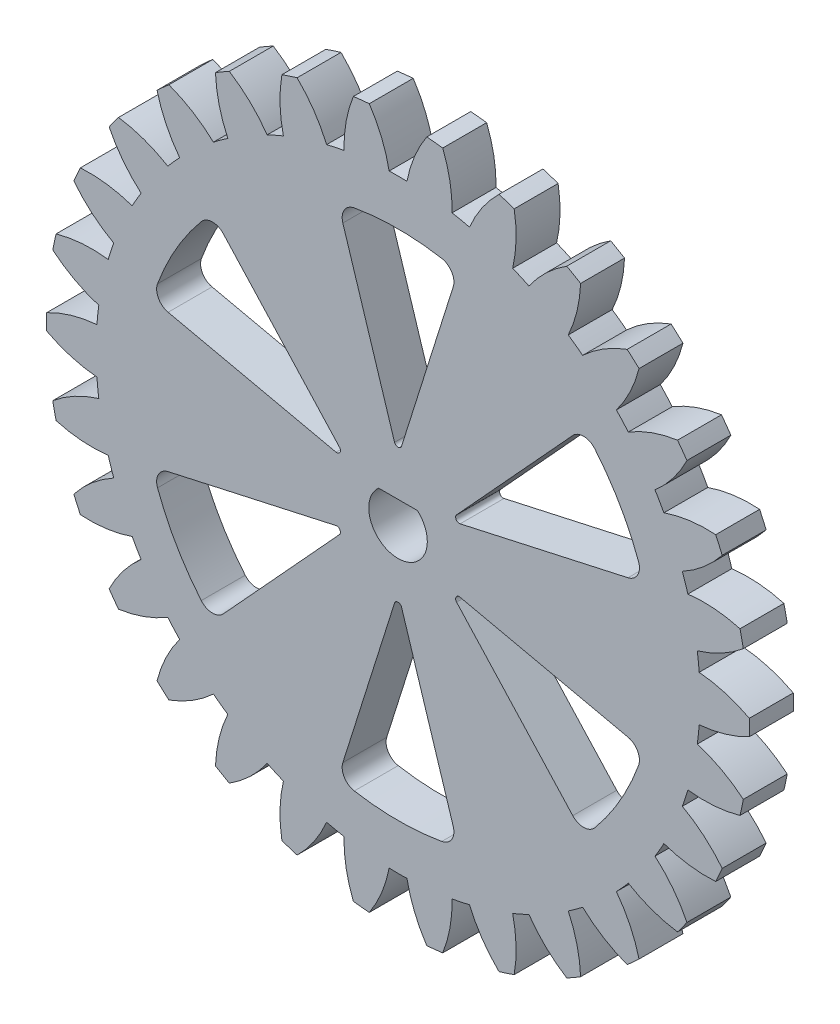
SolidWorks part; units mm, degrees
ref_plane "Front Plane" through (0, 0, 0) normal (0, 0, 1) x (1, 0, 0)
ref_plane "Top Plane" through (0, 0, 0) normal (0, 1, 0) x (1, 0, 0)
ref_plane "Right Plane" through (0, 0, 0) normal (1, 0, 0) x (0, 0, -1)
sketch "Sketch1" plane through (0, 0, 0) normal (0, 0, 1) x (1, 0, 0)
  circle A0 centre (0, 0) radius 24
  dimension "addendumDiameter" = 48
extrude "Boss-Extrude1" add sketch "Sketch1" along normal blind 3
sketch "Sketch2" plane through (0, 0, 3) normal (0, 0, 1) x (1, 0, 0)
  circle A0 centre (0, 0) radius 22.5 construction
  circle A1 centre (0, 0) radius 21.1431 construction
  circle A2 centre (0, 0) radius 20.625 construction
  dimension "D1" = 41.25
  dimension "D2" = 42.2862
  dimension "D3" = 45
sketch "Sketch3" plane through (0, 0, 3) normal (0, 0, 1) x (1, 0, 0)
  line L0 (0, 0) -> (0, 38.0024) construction
  line L1 (0, 0) -> (-1.8856, 17.9401) construction
  line L2 (-1.177, 22.4692) -> (-2.3487, 22.346) construction
  arc A0 (-1.965, 23.9194) -> (-0.6079, 20.616) centre (-9.4458, 18.9158) cw
  circle A1 centre (0, 0) radius 21.1431 construction
  circle A2 centre (0, 0) radius 24 construction
  circle A3 centre (0, 0) radius 20.625 construction
  arc A4 (1.965, 23.9194) -> (0.6079, 20.616) centre (9.4458, 18.9158) ccw
  arc A5 (-1.965, 23.9194) -> (1.965, 23.9194) centre (0, 0) cw
  arc A6 (0.6079, 20.616) -> (-0.6079, 20.616) centre (0, 0) ccw
  circle A7 centre (0, 0) radius 22.5 construction
  dimension "D2" = 9
  dimension "D1" = 6
  dimension "D3" = 1.1781
extrude "Cut-Extrude1" cut sketch "Sketch3" against normal through all
ref_axis "Axis2" through (0, 0, 3) along (0, 0, -1)
pattern_circular "CirPattern1" count 30 over 360 about axis through (0, 0, 3) along (0, 0, -1) of "Cut-Extrude1"
sketch "Sketch7" [suppressed] plane through (0, 0, 6.36) normal (0, 0, 1) x (1, 0, 0)
  circle A0 centre (0, 0) radius 2.6
  dimension "D1" = 5.2
sketch "Sketch9" plane through (0, 0, 3) normal (0, 0, 1) x (1, 0, 0)
  line L0 (-1.3229, 1.5) -> (1.3229, 1.5)
  arc A0 (-1.3229, 1.5) -> (1.3229, 1.5) centre (0, 0) ccw
  point P5 (0, 1.5)
  dimension "D1" = 4
  dimension "D2" = 1.5
extrude "Cut-Extrude7" cut sketch "Sketch9" against normal blind 10
sketch "Sketch10" plane through (0, 0, 3) normal (0, 0, 1) x (1, 0, 0)
  line L0 (0, 4) -> (-4.1028, 17.0123)
  line L2 (4.1028, 17.0123) -> (0, 4)
  arc A0 (-4.1028, 17.0123) -> (4.1028, 17.0123) centre (0, 0) cw
  arc A1 (-1.3229, 1.5) -> (1.3229, 1.5) centre (0, 0) ccw construction
  dimension "D1" = 17.5
  dimension "D3" = 4
  dimension "D4" = 35
ref_axis "Axis3" through (0, 0, 3) along (0, 0, 1)
extrude "Cut-Extrude8" cut sketch "Sketch10" against normal through all both and the other way through all
fillet "Fillet1" radius 1 2 edges at (4.1028, 17.0123, 1.5) (-4.1028, 17.0123, 1.5)
fillet "Fillet2" radius 0.25 1 edges at (0, 4, 1.5)
pattern_circular "CirPattern2" count 6 over 360 about axis through (0, 0, 3) along (0, 0, 1) of "Fillet2", "Cut-Extrude8", "Fillet1"
equation "\"module\"= 1.5"
equation "\"teeth\"= 30"
equation "\"pressureAngle\"= 20deg"
equation "\"gearThickness\"= 3mm"
equation "\"addendumFactor\"= 1"
equation "\"dedendumFactor\"= 1.25"
equation "\"pitch\"= 1 / \"module\""
equation "\"pitchDiameter\"= \"teeth\" / \"pitch\""
equation "\"addendum\"= \"addendumFactor\" / \"pitch\""
equation "\"dedendum\"= \"dedendumFactor\" / \"pitch\""
equation "\"D1@Boss-Extrude1\"=\"gearThickness\""
equation "\"D1@Sketch2\"=\"pitchDiameter\" - 2* \"dedendum\""
equation "\"D2@Sketch2\"=\"pitchDiameter\" * cos(\"pressureAngle\")"
equation "\"D3@Sketch2\"=\"pitchDiameter\""
equation "\"D1@Sketch3\"=180/\"teeth\""
equation "\"D2@Sketch3\"=\"pitchDiameter\"/5"
equation "\"D3@Sketch3\"=PI/2/\"pitch\"/2"
equation "\"D1@CirPattern1\"=\"teeth\""
equation "\"addendumDiameter@Sketch1\"=\"pitchDiameter\" + 2* \"addendum\""
equation "\"D2@CirPattern1\"=360/\"teeth\""
equation "\"D1@Sketch10\"=\"pitchDiameter\"/2 -5"
